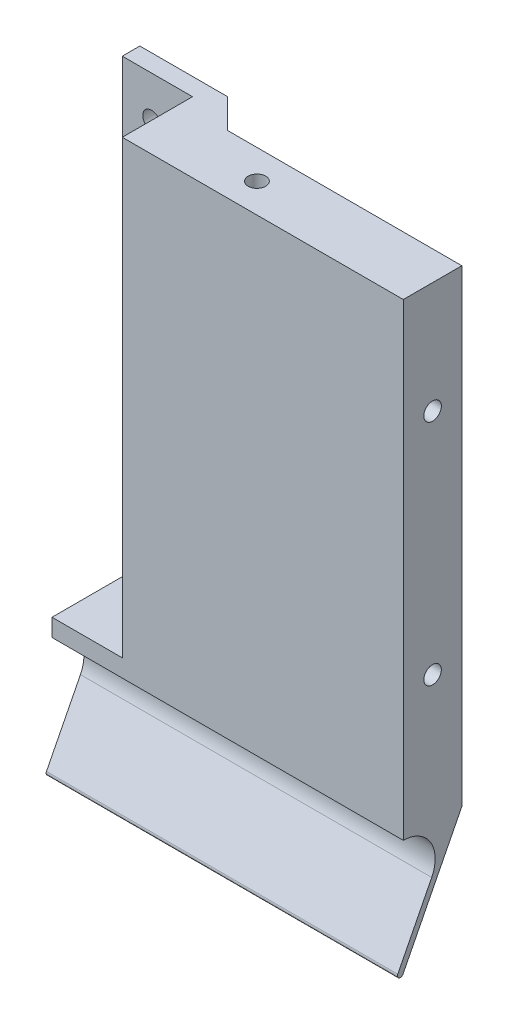
SolidWorks part; units mm, degrees
ref_plane "Front Plane" through (0, 0, 0) normal (0, 0, 1) x (1, 0, 0)
ref_plane "Top Plane" through (0, 0, 0) normal (0, 1, 0) x (1, 0, 0)
ref_plane "Right Plane" through (0, 0, 0) normal (1, 0, 0) x (0, 0, -1)
sketch "Sketch2" plane through (0, 0, 0) normal (0, 1, 0) x (1, 0, 0)
  line L0 (-95.6969, 16.5556) -> (-83.6969, 16.5556)
  line L1 (-83.6969, 16.5556) -> (-83.6969, 4.5556)
  line L2 (-83.6969, 4.5556) -> (-35.6969, 4.5556)
  line L3 (-35.6969, 4.5556) -> (-35.6969, 14.5556)
  line L4 (-35.6969, 14.5556) -> (-80.6969, 14.5556)
  line L5 (-80.6969, 14.5556) -> (-80.6969, 19.5556)
  line L6 (-80.6969, 19.5556) -> (-95.6969, 19.5556)
  line L7 (-95.6969, 19.5556) -> (-95.6969, 16.5556)
  line L8 (-83.6969, 4.5556) -> (-95.6969, 4.5556)
  line L9 (-95.6969, 4.5556) -> (-95.6969, 16.5556)
  point P7 (-80.6969, 17.0556)
  dimension "D1" = 12
  dimension "D2" = 12
  dimension "D3" = 10
  dimension "D4" = 3
  dimension "D5" = 3
  dimension "D6" = 60
extrude "Boss-Extrude1" add sketch "Sketch2" along normal blind 80 contours L6 L7 L0 L1 L2 L3 L4 L5 region at (-62.3664, 0, -10.3437)
extrude "Boss-Extrude2" add sketch "Sketch2<3>" along normal blind 3 from surface contours L9 L8 L1 L0 region at (-89.6969, 0, -10.5556) starting at face at (-73.9469, 0, -13.8056)
sketch "Sketch2<3>" plane through (0, 0, 0) normal (0, 1, 0) x (1, 0, 0) same geometry as "Sketch2"
ref_plane "Plane1" through (-83.6969, 0, 0) normal (-1, 0, 0) x (0, 0, 1)
sketch "Sketch4" plane through (-83.6969, 0, 0) normal (-1, 0, 0) x (0, 0, 1)
  line L0 (-4.5556, 80) -> (-4.5556, 3) construction
  line L1 (-16.5556, 80) -> (-16.5556, 3) construction
  line L3 (-16.5556, 80) -> (-4.5556, 80) construction
  line L4 (-4.5556, 3) -> (-16.5556, 3) construction
  circle A0 centre (-9.5556, 22) radius 1.5
  circle A1 centre (-9.5556, 61) radius 1.5
  dimension "D1" = 3
  dimension "D2" = 5
  dimension "D3" = 7
  dimension "D4" = 19
  dimension "D5" = 19
extrude "Cut-Extrude1" cut sketch "Sketch4" against normal through all
ref_plane "Plane2" through (0, 0, -16.5556) normal (0, 0, 1) x (1, 0, 0)
sketch "Sketch5" plane through (0, 0, -16.5556) normal (0, 0, 1) x (1, 0, 0)
  line L0 (-95.6969, 80) -> (-95.6969, 3) construction
  line L2 (-83.6969, 3) -> (-95.6969, 3) construction
  line L3 (-95.6969, 80) -> (-83.6969, 80) construction
  circle A0 centre (-90.6969, 10) radius 1.5
  circle A1 centre (-90.6969, 73) radius 1.5
  dimension "D1" = 3
  dimension "D2" = 5
  dimension "D3" = 7
  dimension "D4" = 7
extrude "Cut-Extrude2" cut sketch "Sketch5" against normal through all
ref_plane "Plane3" through (0, 0, -14.5556) normal (0, 0, -1) x (-1, 0, 0)
sketch "Sketch6" plane through (0, 0, -14.5556) normal (0, 0, -1) x (-1, 0, 0)
  line L0 (80.6969, 57.5) -> (35.6969, 57.5) construction
  line L1 (35.6969, 80) -> (35.6969, 0) construction
  line L2 (80.6969, 80) -> (80.6969, 0) construction
  line L5 (35.6969, 80) -> (80.6969, 80) construction
  line L6 (67.7232, 63) -> (70.8986, 57.5)
  line L7 (70.8986, 57.5) -> (67.7232, 52)
  line L8 (48.6706, 63) -> (45.4952, 57.5)
  line L9 (45.4952, 57.5) -> (48.6706, 52)
  circle A0 centre (58.1969, 57.5) radius 11
  circle A1 centre (58.1969, 57.5) radius 4
  dimension "D1" = 8
  dimension "D2" = 22
  dimension "D3" = 22.5
  dimension "D4" = 22.5
  dimension "D5" = 60
extrude "Cut-Extrude3" cut sketch "Sketch6" against normal blind 8 contours L0 A0 L8 | A0 L0 L9 | L0 A0 A1 | A0 L0 A1 | L0 L6 A0 | L7 L0 A0 | A1 region at (-69.5661, 56.0862, -14.5556) region at (-69.5661, 58.9138, -14.5556) region at (-58.1969, 52.3787, -14.5556) region at (-58.1969, 62.6213, -14.5556) region at (-46.8277, 58.9138, -14.5556) region at (-46.8277, 56.0862, -14.5556)
ref_plane "Plane4" through (0, 80, 0) normal (0, 1, 0) x (1, 0, 0)
sketch "Sketch7" plane through (0, 80, 0) normal (0, 1, 0) x (1, 0, 0)
  line L0 (-65.6969, 4.5556) -> (-65.6969, 14.5556) construction
  line L1 (-83.6969, 4.5556) -> (-35.6969, 4.5556) construction
  line L2 (24.75, 14.5556) -> (-24.75, 14.5556) construction
  line L4 (-35.6969, 4.5556) -> (-35.6969, 14.5556) construction
  circle A0 centre (-65.6969, 9.5556) radius 1.5
  dimension "D1" = 3
  dimension "D2" = 30
extrude "Cut-Extrude5" cut sketch "Sketch7" against normal blind 20
ref_plane "Plane5" through (-35.6969, 0, 0) normal (1, 0, 0) x (0, 0, -1)
sketch "Sketch8" plane through (-35.6969, 0, 0) normal (1, 0, 0) x (0, 0, -1)
  line L0 (14.5556, 0) -> (4.5013, -19.7808)
  line L1 (4.5556, 0) -> (14.5556, 0) construction
  line L2 (3.6098, -19.3277) -> (9.411, -7.9145)
  line L3 (9.411, -7.9145) -> (10.3024, -8.3677) construction
  line L4 (3.5556, -4.1228) -> (3.5556, -12.8593) construction
  line L5 (4.5556, 80) -> (4.5556, 0) construction
  line L6 (4.5556, 0) -> (14.5556, 0)
  arc A0 (4.5013, -19.7808) -> (3.6098, -19.3277) centre (4.0556, -19.5543) cw
  arc A1 (9.411, -7.9145) -> (4.5556, 0) centre (4.5556, -5.4466) ccw
  point P12 (3.829, -20)
  dimension "D2" = 0.5
  dimension "D1" = 1
  dimension "D3" = 20
  dimension "D4" = 1
extrude "Boss-Extrude3" add sketch "Sketch8" against normal up to surface (60 mm away) up to face at (-95.6969, 27.6667, -13.5556)
chamfer "Chamfer1" distance 5 angle 45 1 edges at (-80.6969, 40, -14.5556)
